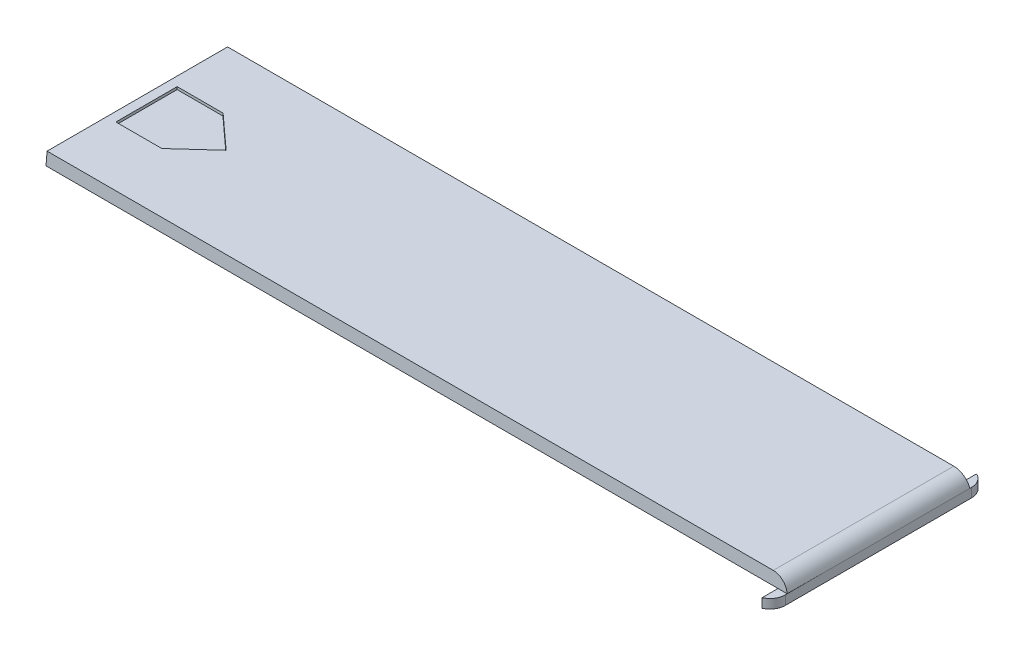
SolidWorks part; units mm, degrees
ref_plane "Front" through (0, 0, 0) normal (0, 0, 1) x (1, 0, 0)
ref_plane "Top" through (0, 0, 0) normal (0, 1, 0) x (1, 0, 0)
ref_plane "Right" through (0, 0, 0) normal (1, 0, 0) x (0, 0, -1)
sketch "Sketch2" plane through (0, 0, 0) normal (0, 1, 0) x (1, 0, 0)
  line L0 (-121.412, 0) -> (-1.651, 0) construction
  line L1 (-121, 0) -> (0, 0)
  line L3 (-121.412, 29.8196) -> (-1.651, 29.8196) construction
  line L4 (-121, 29.8196) -> (0, 29.8196)
  line L6 (-121, 29.8196) -> (-121, 0)
  line L7 (0, 0) -> (0, 29.8196)
  line L8 (0, -50) -> (0, 50) construction
  dimension "D1" = 121
extrude "Base-Extrude" add sketch "Sketch2" along normal blind 2
draft "Draft1" type of draft neutral plane draft angle 5 neutral plane "Top" faces to draft 2 face at (-60.5, 1, 0) face at (-60.5, 1, -29.8196) neutral plane through (0, 0, 0) neutral plane normal (0, 1, 0) parameters "D1"=5
fillet "Fillet3" radius 2.5 1 edges at (0, 2, -14.9098)
sketch "Sketch3" plane through (0, 0, 0) normal (0, -1, 0) x (1, 0, 0)
  line L5 (0, 0) -> (0, -29.8196) construction
  line L10 (0, 0.2989) -> (0, -30.1185)
  line L11 (-1.5, -32.4098) -> (-1.5, 2.5902)
  arc A2 (-1.5, -32.4098) -> (0, -30.1185) centre (-2.5, -30.1185) ccw
  arc A4 (0, 0.2989) -> (-1.5, 2.5902) centre (-2.5, 0.2989) ccw
  point P5 (0, -14.9098)
  point P6 (0, -14.9098)
  dimension "D2" = 2.5
  dimension "D1" = 35
  dimension "D3" = 1.5
extrude "Boss-Extrude1" add sketch "Sketch3" along normal blind 1.5
sketch "Sketch4" plane through (0, 0, 0) normal (0, -1, 0) x (1, 0, 0)
  line L0 (-120.25, -18.4698) -> (-121.75, -18.4698)
  line L1 (-119, -17.2198) -> (-119, -12.5998)
  line L2 (-121.75, -11.3498) -> (-120.25, -11.3498)
  line L3 (-123, -12.5998) -> (-123, -17.2198)
  line L5 (-123.1387, -18.7198) -> (-121.412, -18.7198) construction
  line L6 (-123.1387, -11.0998) -> (-121.412, -11.0998) construction
  line L8 (-121, -29.8196) -> (-121, 0) construction
  arc A0 (-120.25, -11.3498) -> (-119, -12.5998) centre (-120.25, -12.5998) cw
  arc A1 (-119, -17.2198) -> (-120.25, -18.4698) centre (-120.25, -17.2198) cw
  arc A2 (-123, -17.2198) -> (-121.75, -18.4698) centre (-121.75, -17.2198) ccw
  arc A3 (-123, -12.5998) -> (-121.75, -11.3498) centre (-121.75, -12.5998) cw
  dimension "D4" = 1.25
  dimension "D1" = 0.25
  dimension "D2" = 0.25
  dimension "D3" = 4
  dimension "D5" = 2
extrude "Boss-Extrude2" add sketch "Sketch4" along normal blind 2
sketch "Sketch5" plane through (-217.9276, 2, 0) normal (0, -1, 0) x (1, 0, 0)
  line L0 (105.9276, -19.9098) -> (98.4276, -19.9098)
  line L1 (96.9276, -29.6446) -> (96.9276, -0.175) construction
  line L2 (98.4276, -9.9098) -> (105.9276, -9.9098)
  line L3 (98.4276, -9.9098) -> (98.4276, -19.9098)
  line L4 (105.9276, -9.9098) -> (111.4276, -14.9098)
  line L5 (111.4276, -14.9098) -> (105.9276, -19.9098)
  point P5 (96.9276, -14.9098)
  dimension "D1" = 10
  dimension "D2" = 7.5
  dimension "D3" = 13
  dimension "D4" = 1.5
extrude "Cut-Extrude3" cut sketch "Sketch5" along normal blind 0.4 draft 3
